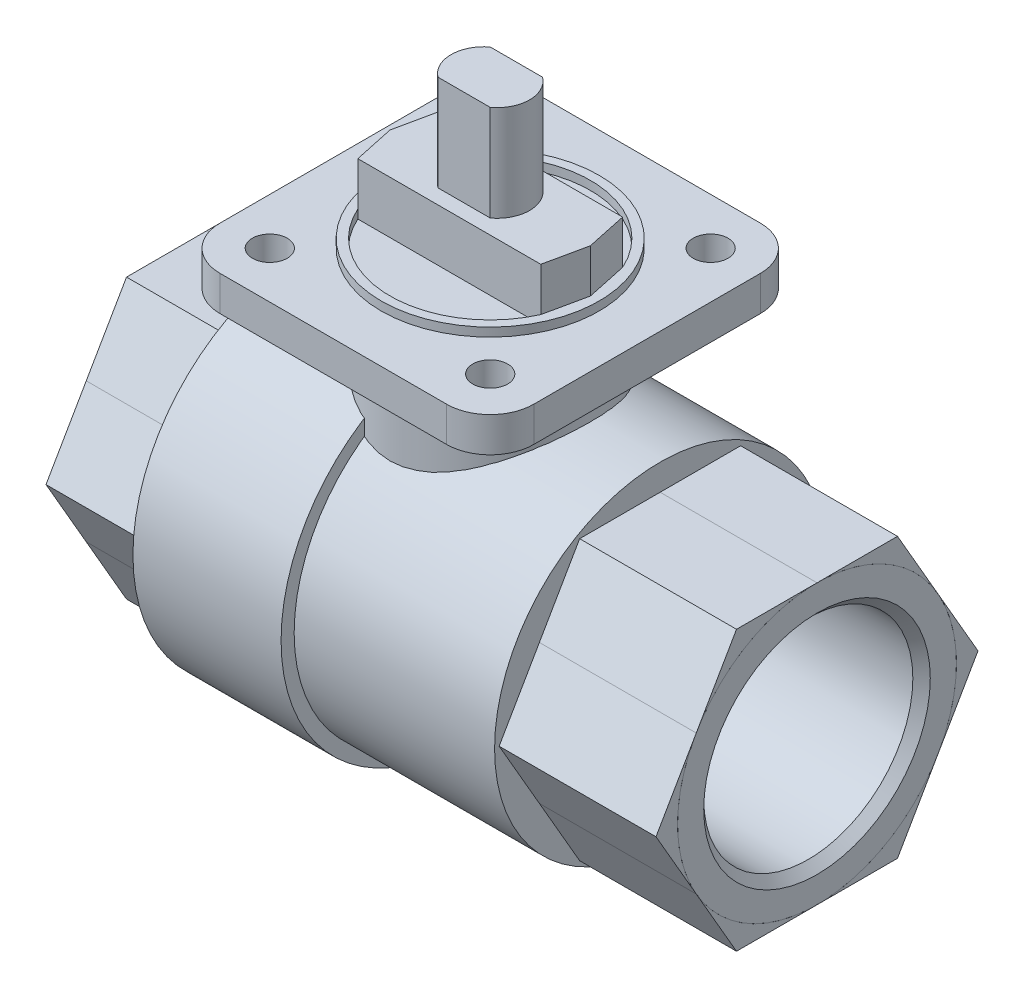
SolidWorks part; units mm, degrees
ref_plane "Front Plane" through (0, 0, 0) normal (0, 0, 1) x (1, 0, 0)
ref_plane "Top Plane" through (0, 0, 0) normal (0, 1, 0) x (1, 0, 0)
ref_plane "Right Plane" through (0, 0, 0) normal (1, 0, 0) x (0, 0, -1)
sketch "Szkic1" plane through (0, 0, 0) normal (0, 0, 1) x (1, 0, 0)
  line L0 (0, 0) -> (0, 32)
  line L1 (0, 32) -> (17, 32)
  line L2 (17, 32) -> (17, 0)
  line L3 (17, 0) -> (0, 0)
  line L4 (17, 32) -> (17, 30)
  line L5 (17, 0) -> (17, 2)
  line L6 (17, 2) -> (47, 2)
  line L7 (47, 2) -> (47, 30)
  line L8 (47, 30) -> (17, 30)
  line L9 (47, 30) -> (47, 32)
  line L10 (47, 32) -> (70, 32)
  line L11 (70, 32) -> (70, 0)
  line L12 (70, 0) -> (47, 0)
  line L13 (47, 0) -> (47, 2)
  line L14 (47, 2) -> (47, 0)
  line L15 (47, 2) -> (47, 30)
  line L16 (17, 2) -> (17, 30)
  line L17 (17, 30) -> (47, 30)
  line L18 (47, 2) -> (17, 2)
  line L19 (47, 2) -> (47, 0)
  line L20 (70, 0) -> (70, 32)
  line L21 (47, 32) -> (47, 30)
  line L22 (47, 32) -> (47, 30)
  line L23 (0, 32) -> (12, 32)
  line L24 (0, 0) -> (11, 0)
  line L25 (0, 32) -> (0, 28)
  line L26 (0, 28) -> (70, 28)
  line L27 (0, 0) -> (0, 4)
  line L28 (0, 4) -> (70, 4)
  line L29 (12, 32) -> (12, 36.5)
  line L30 (12, 36.5) -> (29, 36.5)
  line L31 (0, 16) -> (70, 16)
  line L32 (29, 36.5) -> (29, 35)
  line L33 (29, 35) -> (52, 35)
  line L34 (52, 35) -> (52, 32)
  line L35 (17, 30) -> (17, 26)
  line L36 (17, 26) -> (47, 26)
  line L37 (47, 26) -> (47, 30)
  dimension "D1" = 32
  dimension "D2" = 17
  dimension "D3" = 2
  dimension "D4" = 2
  dimension "D5" = 30
  dimension "D6" = 18
  dimension "D7" = 12
  dimension "D8" = 4
  dimension "D9" = 4
  dimension "D10" = 4.5
  dimension "D11" = 17
  dimension "D12" = 1.5
  dimension "D13" = 23
  dimension "D14" = 70
  dimension "D15" = 4
revolve "Obrót2" add sketch "Szkic1" angle 360 about L31 region at (8.5, 30, 0) region at (32, 27, 0) region at (32, 29, 0) region at (30.573, 33.0493, 0) region at (58.5, 30, 0)
sketch "Szkic2" plane through (0, 0, 0) normal (1, 0, 0) x (0, 0, -1)
  line L1 (18.4752, 16) -> (9.2376, 32)
  line L2 (9.2376, 32) -> (-9.2376, 32)
  line L3 (-9.2376, 32) -> (-18.4752, 16)
  line L4 (-18.4752, 16) -> (-9.2376, 0)
  line L5 (-9.2376, 0) -> (9.2376, 0)
  line L6 (9.2376, 0) -> (18.4752, 16)
  circle A0 centre (0, 16) radius 16
  circle A1 centre (0, 16) radius 16 construction
  point P3 (0, 0)
  point P11 (0, 0)
  dimension "D1" = 16
extrude "Dodanie-wyciągnięcie2" add sketch "Szkic2" along normal blind 70 separate body contours A0 L2 L3 | A0 L3 L4 | A0 L4 L5 | A0 L5 L6 | A0 L6 L1 | A0 L1 L2 region at (0, 16, -16.537) region at (0, 30.3215, -8.2685) region at (0, 1.6785, -8.2685) region at (0, 30.3215, 8.2685) region at (0, 1.6785, 8.2685) region at (0, 16, 16.537)
fillet "Zaokrąglenie2" radius 1 1 edges at (0, 16, 12)
chamfer "Sfazowanie1" distance 1 angle 45 1 edges at (70, 16, 12)
sketch "Szkic5" plane through (0, 0, 0) normal (0, 1, 0) x (1, 0, 0)
  line L0 (0, 0) -> (21, 0)
  line L1 (47, 0) -> (17, 0) construction
  line L2 (21, 0) -> (32.5, 0)
  line L3 (32.5, 0) -> (14.5, 0)
  line L4 (14.5, 18) -> (19.5, 18)
  line L6 (14.5, 0) -> (14.5, 18)
  line L7 (14.5, 18) -> (32.5, 18)
  line L8 (32.5, 18) -> (32.5, 0)
  line L9 (14.5, 18) -> (50.5, 18)
  line L10 (14.5, 18) -> (14.5, -18)
  line L11 (14.5, -18) -> (50.5, -18)
  line L12 (50.5, 18) -> (50.5, -18)
  line L13 (14.5, 18) -> (14.5, 13)
  line L14 (50.5, 18) -> (45.5, 18)
  line L15 (50.5, 18) -> (50.5, 13)
  line L16 (14.5, -18) -> (14.5, -13)
  line L17 (14.5, -18) -> (19.5, -18)
  line L18 (50.5, -18) -> (45.5, -18)
  line L19 (50.5, -18) -> (50.5, -13)
  line L20 (19.5, 13) -> (32.5, 0)
  line L21 (45.5, 13) -> (19.5, -13)
  line L22 (45.5, -13) -> (32.5, 0)
  line L23 (45.5, -13) -> (45, -12.5)
  line L24 (45.5, 13) -> (45.1464, 12.6464)
  line L25 (19.5, 13) -> (19.8536, 12.6464)
  line L26 (19.5, -13) -> (19.8536, -12.6464)
  circle A0 centre (32.5, 0) radius 11.5
  arc A2 (14.5, 13) -> (19.5, 18) centre (19.5, 13) cw
  arc A3 (19.5, -18) -> (14.5, -13) centre (19.5, -13) cw
  arc A4 (50.5, -13) -> (45.5, -18) centre (45.5, -13) cw
  arc A5 (45.5, 18) -> (50.5, 13) centre (45.5, 13) cw
  circle A10 centre (19.8536, 12.6464) radius 2
  circle A11 centre (45.1464, 12.6464) radius 2
  circle A12 centre (45, -12.5) radius 2
  circle A13 centre (19.8536, -12.6464) radius 2
  dimension "D15" = 0.5
  dimension "D16" = 0.5
  dimension "D17" = 0.5
  dimension "D18" = 0.5
  dimension "D19" = 4
  dimension "D20" = 4
  dimension "D21" = 4
  dimension "D22" = 4
  dimension "D1" = 21
  dimension "D2" = 11.5
  dimension "D3" = 18
  dimension "D4" = 18
  dimension "D5" = 36
  dimension "D6" = 36
  dimension "D7" = 5
  dimension "D8" = 5
  dimension "D9" = 5
  dimension "D10" = 5
  dimension "D11" = 5
  dimension "D12" = 5
  dimension "D13" = 5
  dimension "D14" = 5
extrude "Dodanie-wyciągnięcie3" add sketch "Szkic5" along normal blind 10 and the other way blind 6 from offset 36.5 separate body contours A0
extrude "Dodanie-wyciągnięcie5" add sketch "Szkic5<12>" along normal blind 4 from offset 42.5 separate body contours A2 L6 L0 A0 L8 L7 | A5 L9 L8 A0 L0 L10 A3 L11 A4 L12 region at (14.7546, 0, -6.5) region at (17.75, 0, 0.5091)
sketch "Szkic5<12>" plane through (0, 0, 0) normal (0, 1, 0) x (1, 0, 0) same geometry as "Szkic5"
sketch "Szkic7" plane through (0, 0, 0) normal (0, 1, 0) x (1, 0, 0)
  line L0 (32.5, 0) -> (21, 0)
  line L1 (21, 0) -> (22.0017, 4.6941)
  line L2 (22.0017, 4.6941) -> (32.5, 4.6941)
  line L3 (32.5, 4.6941) -> (32.5, 0)
  line L5 (21, 0) -> (22.0017, -4.6941)
  line L6 (22.0017, -4.6941) -> (32.5, -4.6941)
  line L7 (32.5, -4.6941) -> (32.5, 0)
  line L9 (32.5, 4.6941) -> (42.9983, 4.6941)
  line L10 (42.9983, 4.6941) -> (44, 0)
  line L11 (44, 0) -> (32.5, 0)
  line L12 (32.5, -4.6941) -> (42.9983, -4.6941)
  line L13 (42.9983, -4.6941) -> (44, 0)
  line L14 (32.5, 0) -> (32.5, 3.0011)
  line L15 (32.5, 3.0011) -> (32.5, -2.9989)
  line L16 (32.5, -2.9989) -> (35.5, -2.9989)
  line L17 (35.5, -2.9989) -> (35.5, 3.0011)
  line L18 (35.5, 3.0011) -> (29.5, 3.0011)
  line L19 (29.5, 3.0011) -> (29.5, -2.9989)
  line L20 (29.5, -2.9989) -> (32.5, -2.9989)
  line L21 (32.5, 0) -> (28, 0)
  line L22 (28, 0) -> (37, 0)
  circle A0 centre (32.5, 0) radius 11.5 construction
  circle A1 centre (32.5, 0) radius 11.5 construction
  arc A2 (29.5, 3.0011) -> (29.5, -2.9989) centre (31.7744, 0.0011) ccw
  arc A3 (35.5, -2.9989) -> (35.5, 3.0011) centre (33.2883, 0.0011) ccw
  circle A4 centre (32.5, 0) radius 12.5
  circle A5 centre (32.5, 0) radius 11.5
  dimension "D6" = 25
  dimension "D1" = 3
  dimension "D2" = 3
  dimension "D3" = 6
  dimension "D4" = 4.5
  dimension "D5" = 9
extrude "Dodanie-wyciągnięcie6" add sketch "Szkic7" along normal blind 6 from offset 46.5 separate body contours A2 L18 L3 L2 L1 L0 L22 | A2 L22 L0 L5 L6 L7 L20 | A3 L16 L7 L12 L13 L11 | A3 L11 L10 L9 L3 L18 region at (25.9353, 0, 2.5872) region at (25.9342, 0, -2.5871) region at (39.0692, 0, -2.5891) region at (39.0681, 0, 2.5891)
extrude "Dodanie-wyciągnięcie7" add sketch "Szkic7<4>" along normal blind 17 from offset 46.5 contours L0 A2 L19 | L19 A2 L0 | L18 L19 L0 L3 | L19 L20 L7 L0 | L17 L18 L3 L11 | L16 L17 L11 L7 | L11 A3 L17 | L17 A3 L11 region at (28.8924, 0, -1.1626) region at (28.8925, 0, 1.1616) region at (31, 0, -1.5006) region at (31, 0, 1.4994) region at (34, 0, 1.4994) region at (34, 0, -1.5006) region at (36.1182, 0, -1.1638) region at (36.1181, 0, 1.1628)
sketch "Szkic7<4>" plane through (0, 0, 0) normal (0, 1, 0) x (1, 0, 0) same geometry as "Szkic7"
extrude "Dodanie-wyciągnięcie12" add sketch "Szkic7<7>" along normal blind 1 from offset 46.5 contours A4 A5 | L1 A5 | L5 A5 | L13 A5 | L10 A5 region at (21.4017, 0, -2.3682) region at (21.4017, 0, 2.3682) region at (43.5983, 0, -2.3682) region at (43.5983, 0, 2.3682) region at (20.3536, 0, 0)
sketch "Szkic7<7>" plane through (0, 0, 0) normal (0, 1, 0) x (1, 0, 0) same geometry as "Szkic7"
